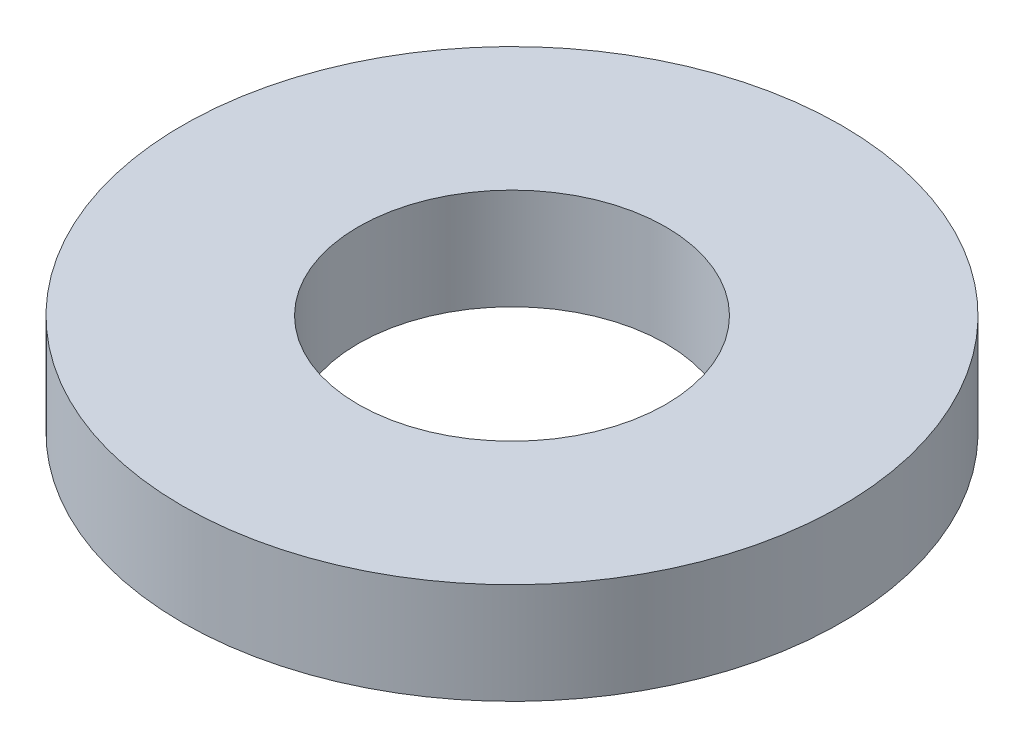
SolidWorks part; units mm, degrees
ref_plane "Front Plane" through (0, 0, 0) normal (0, 0, 1) x (1, 0, 0)
ref_plane "Top Plane" through (0, 0, 0) normal (0, 1, 0) x (1, 0, 0)
ref_plane "Right Plane" through (0, 0, 0) normal (1, 0, 0) x (0, 0, -1)
sketch "Sketch1" plane through (0, 0, 0) normal (0, 1, 0) x (1, 0, 0)
  circle A0 centre (0, 0) radius 75
  dimension "FLANGE_OD" = 150
extrude "Boss-Extrude1" add sketch "Sketch1" along normal blind 23
sketch "Sketch2" plane through (0, 0, 0) normal (0, 1, 0) x (1, 0, 0)
  circle A0 centre (0, 0) radius 35
  dimension "BORE_D" = 70
extrude "Cut-Extrude1" cut sketch "Sketch2" along normal through all
sketch "Sketch3" plane through (0, 23, 0) normal (0, 1, 0) x (1, 0, 0)
  circle A0 centre (0, 0) radius 27.4761 construction
  circle A1 centre (-27.4761, 0) radius 5.6704
  dimension "BOLT_D" = 11.3409
  dimension "BOLT_PCD" = 54.9522
extrude "Cut-Extrude2" cut sketch "Sketch3" against normal blind 20.9396 rebuild error yes
pattern_circular "CirPattern1" count 5 over 360 rebuild error yes
